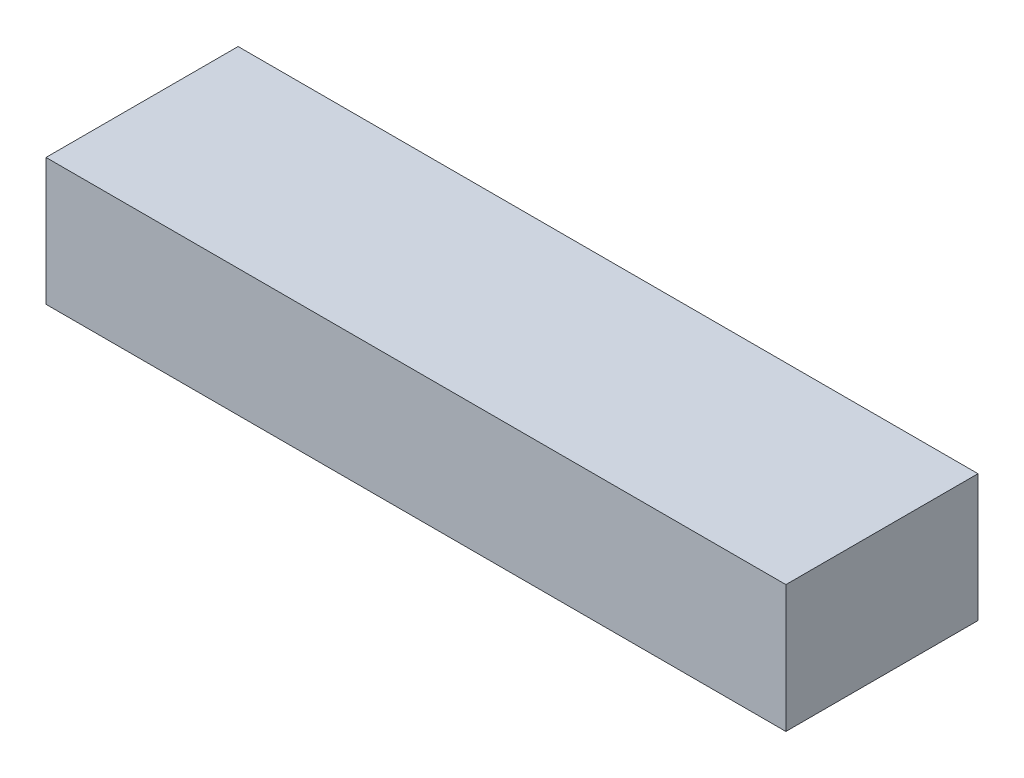
SolidWorks part; units mm, degrees
ref_plane "Front Plane" through (0, 0, 0) normal (0, 0, 1) x (1, 0, 0)
ref_plane "Top Plane" through (0, 0, 0) normal (0, 1, 0) x (1, 0, 0)
ref_plane "Right Plane" through (0, 0, 0) normal (1, 0, 0) x (0, 0, -1)
sketch "Sketch1" plane through (0, 0, 0) normal (0, 1, 0) x (1, 0, 0)
  line L1 (570, -148) -> (-570, -148)
  line L2 (570, -148) -> (570, 148)
  line L3 (570, 148) -> (-570, 148)
  line L4 (-570, -148) -> (-570, 148)
  line L5 (570, -148) -> (-570, 148) construction
  line L6 (570, 148) -> (-570, -148) construction
  point P0 (0, 0)
  dimension "D1" = 1140
  dimension "D2" = 296
extrude "Boss-Extrude1" add sketch "Sketch1" along normal blind 196
equation "\"thickness 1\" = 2"
equation "\"thickness 2\"= 3"
equation "\"connecting flange\"= 35"
equation "\"main length\"= 1200"
equation "\"main width\"= 1200"
equation "\"divider panel distance offset\"= 296"
equation "\"access hatch length\" = \"access hatch cutout length\" + \"access hatch offset\" * 2"
equation "\"access hatch width\" = \"access hatch cutout width\" + \"access hatch offset\" * 2"
equation "\"side panel length\"= 1200"
equation "\"side panel width\"= 950"
equation "\"drift eliminator size offset\"= 10"
equation "\"drift eliminator depth\" = \"divider panel distance offset\""
equation "\"D2@Sketch1\"=\"drift eliminator depth\""
equation "\"thickness radius 1\"= 3.7366"
equation "\"connecting flange holes\"= 8"
equation "\"connecting flange hole gap\"= 100"
equation "\"cut out flange\"= 15 "
equation "\"top panel slot length\"= 250"
equation "\"top panel slot width\"= 700"
equation "\"access hatch cutout length\"= 400"
equation "\"access hatch cutout width\"= 600"
equation "\"access hatch cutout offset X\"= 100"
equation "\"access hatch cutout offset Y\"= 100"
equation "\"slotted panel length\" = \"main length\" + 100"
equation "\"slotted panel width\" = \"main width\""
equation "\"slot count x\"= 3"
equation "\"slot count y\"= 11"
equation "\"slot offset\" = \"water tray depth\""
equation "\"slot length\"= 30"
equation "\"slot width\"= 200"
equation "\"slot offset x\" = \"slot length\" + \"slot offset\""
equation "\"slot offset y\" = \"slot width\" + \"slot offset\""
equation "\"guide rail flange\"= 40"
equation "\"guid rail flange mount side\"= 20"
equation "\"guid rail back length\" = \"main width\" - \"guide rail flange\" * 2"
equation "\"splash plate length\"= 400"
equation "\"splash plate width\" = \"main width\""
equation "\"splash plate air gap\"= 200"
equation "\"splash plate slot count\"= 11"
equation "\"splash plate slot length\"= 50"
equation "\"splash plate slot height\"= 50"
equation "\"splash plate slot offset\"= 65"
equation "\"water tray depth\"= 150"
equation "\"water tray width\"= 200"
equation "\"water tray panel length\"= 473"
equation "\"dimpled panel length\" = \"main length\" - 200 - \"water tray depth\"/2"
equation "\"dimpled panel top offset\" = \"water tray depth\"/2"
equation "\"dimpled panel width\" = \"main width\""
equation "\"dimple panel slot count\"= 119"
equation "\"dimple panel slot length\"= 10"
equation "\"dimple panel slot width\"= 5"
equation "\"dimple panel slot offset\"= 10"
equation "\"sump base flat section width\"= 300"
equation "\"sump upper depth\"= 300"
equation "\"sump depth\"= 550"
equation "\"leg length\" = \"sump depth\" + 150"
equation "\"leg width\"= 80"
equation "\"leg depth\"= 40"
equation "\"leg support plate size\" = \"leg width\" - \"thickness 2\" * 2"
equation "\"leg base plate thickness\"= 8"
